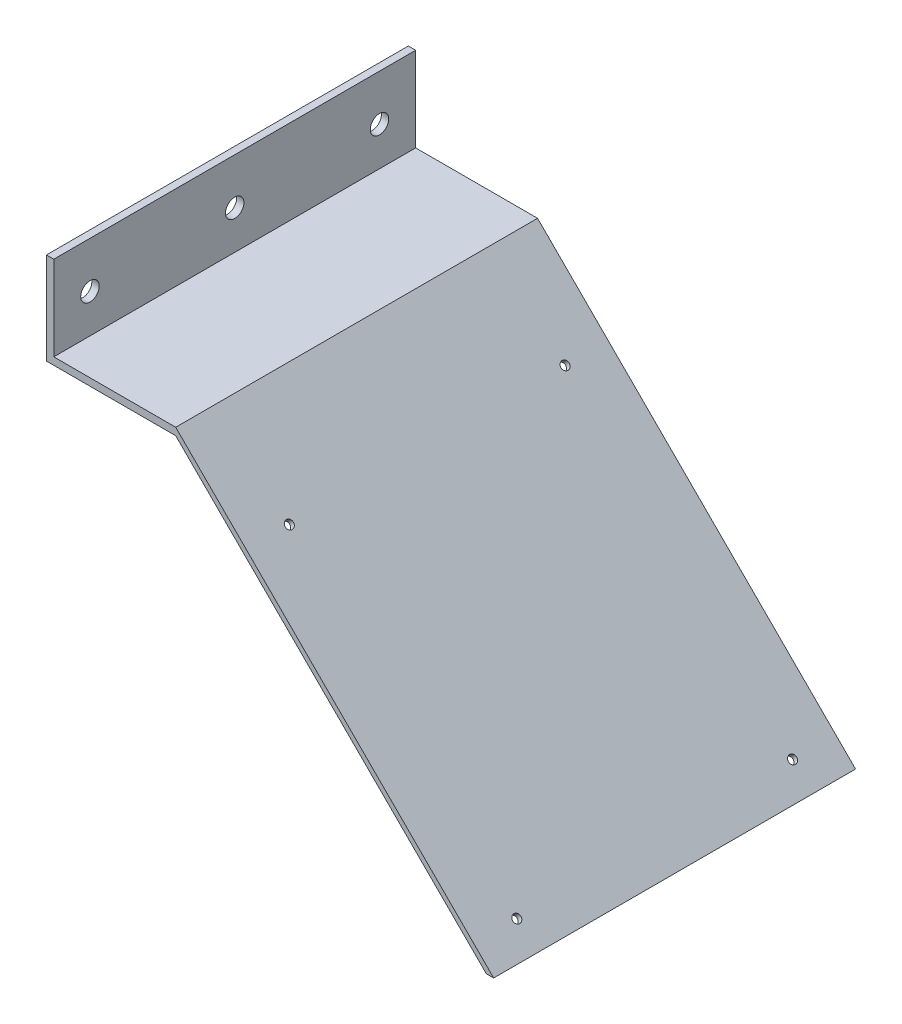
SolidWorks part; units mm, degrees
ref_plane "Front Plane" through (0, 0, 0) normal (0, 0, 1) x (1, 0, 0)
ref_plane "Top Plane" through (0, 0, 0) normal (0, 1, 0) x (1, 0, 0)
ref_plane "Right Plane" through (0, 0, 0) normal (1, 0, 0) x (0, 0, -1)
sketch "Sketch1" plane through (0, 0, 0) normal (0, 0, 1) x (1, 0, 0)
  line L0 (0, 0) -> (85.8336, -85.8336)
  line L9 (85.8336, -85.8336) -> (87.8656, -85.8336)
  line L10 (87.8656, -85.8336) -> (0, 2.032)
  line L12 (0, 2.032) -> (0, 0) construction
  line L13 (0, 0) -> (-35.7216, 0)
  line L14 (0, 0) -> (0, 2.032)
  line L15 (0, 2.032) -> (-35.7216, 2.032)
  line L16 (-35.7216, 0) -> (-35.7216, 2.032)
  line L17 (-35.7216, 0) -> (-33.6896, 0)
  line L18 (-35.7216, 0) -> (-35.7216, 25.4)
  line L19 (-35.7216, 25.4) -> (-33.6896, 25.4)
  line L20 (-33.6896, 0) -> (-33.6896, 25.4)
  line L21 (1.016, 1.016) -> (0, 0) construction
  dimension "D1" = 45
  dimension "D4" = 121.387
  dimension "D2" = 2.032
  dimension "D3" = 35.7216
  dimension "D5" = 25.4
  dimension "D7" = 1.4368
extrude "Boss-Extrude1" add sketch "Sketch1" along normal blind 100 contours L10 L12 L0 L9 | L20 L13 L14 L15 | L15 L20 L19 L18 | L13 L20 L15 L16 region at (43.4268, -42.4068, 0) region at (-16.8448, 1.016, 0) region at (-34.7056, 1.016, 0) region at (-34.7056, 13.716, 0)
sketch "Sketch2" plane through (1.016, 1.016, 0) normal (0.7071, 0.7071, 0) x (0, 0, -1)
  line L0 (-50, -28.087) -> (-50, -113.087) construction
  line L1 (-80, -28.087) -> (-20, -28.087) construction
  line L2 (-80, -28.087) -> (-80, -113.087) construction
  line L3 (-80, -113.087) -> (-20, -113.087) construction
  line L4 (-20, -28.087) -> (-20, -113.087) construction
  line L5 (-75, -35.187) -> (-25, -35.187) construction
  line L6 (-75, -35.187) -> (-75, -105.987) construction
  line L7 (-75, -105.987) -> (-25, -105.987) construction
  line L10 (-25, -35.187) -> (-25, -105.987) construction
  line L11 (-69.455, -33.889) -> (-30.545, -33.889) construction
  line L12 (-69.455, -33.889) -> (-69.455, -107.285) construction
  line L13 (-69.455, -107.285) -> (-30.545, -107.285) construction
  line L14 (-30.545, -33.889) -> (-30.545, -107.285) construction
  line L15 (-80, -70.587) -> (-20, -70.587) construction
  line L17 (-100, -122.8238) -> (0, -122.8238) construction
  line L19 (-100, -122.8238) -> (-100, 1.4368) construction
  line L21 (-88.1, -26.137) -> (-88.1, -115.037) construction
  line L22 (-88.1, -115.037) -> (-11.9, -115.037) construction
  line L23 (-11.9, -115.037) -> (-11.9, -26.137) construction
  line L24 (-11.9, -26.137) -> (-88.1, -26.137) construction
  circle A0 centre (-88.1, -26.137) radius 1.13
  circle A1 centre (-11.9, -26.137) radius 1.13
  circle A2 centre (-11.9, -115.037) radius 1.13
  circle A3 centre (-88.1, -115.037) radius 1.13
  point P6 (-25, -70.587)
  point P10 (-50, -28.087)
  point P13 (-50, -70.587)
  point P17 (-50, -35.187)
  point P23 (-50, -33.889)
  point P24 (-30.545, -70.587)
  point P37 (-50, -26.137)
  point P39 (-11.9, -70.587)
  dimension "D12" = 2.26
  dimension "D2" = 9.7368
  dimension "D3" = 50
  dimension "D11" = 76.2
  dimension "D13" = 88.9
ref_axis "Axis1" through (-9.134, -48.8965, 50) along (1, 0, 0)
extrude "Cut-Extrude1" cut sketch "Sketch2" against normal through all both and the other way through all
hole_wizard "#4-40 Tapped Hole1" positions "3DSketch1" profile "Sketch3" tap size "#4-40" standard "ANSI Inch" end condition through all
sketch3d "3DSketch1"
  point P0 (19.4977, -17.4657, 88.1)
  point P3 (19.4977, -17.4657, 11.9)
  point P6 (82.3594, -80.3274, 11.9)
  point P9 (82.3594, -80.3274, 88.1)
sketch "Sketch3" plane through (19.4977, -17.4657, 88.1) normal (0, 0, 1) x (-0.7071, 0.7071, 0)
  line L0 (0, 0) -> (0, 87.3893)
  line L1 (0, 87.3893) -> (1.1303, 87.3893)
  line L2 (1.1303, 87.3893) -> (1.1303, 0)
  line L5 (1.1303, 0) -> (0, 0)
  line L11 (0, -6.35) -> (0, 107.95) construction
  dimension "Thru Tap Drill Dia." = 2.2606
  dimension "Thru Tap Drill Depth" = 87.3893
cosmetic thread "Hole Thread1" parameters "D2"=2.8448
cosmetic thread "Hole Thread2" parameters "D2"=2.8448
cosmetic thread "Hole Thread3" parameters "D2"=2.8448
cosmetic thread "Hole Thread4" parameters "D2"=2.8448
hole_wizard "1/4-20 Tapped Hole1" positions "Sketch4" profile "Sketch5" tap size "1/4-20" standard "ANSI Inch" end condition through all
sketch "Sketch4" plane through (-35.7216, 0, 0) normal (-1, 0, 0) x (0, 0, 1)
  line L0 (10, 12.7) -> (50, 12.7) construction
  line L1 (50, 12.7) -> (90, 12.7) construction
  line L4 (0, 0) -> (0, 25.4) construction
  point P0 (10, 12.7)
  point P2 (50, 12.7)
  point P4 (90, 12.7)
  dimension "D1" = 80
  dimension "D2" = 10
  dimension "D3" = 12.7
sketch "Sketch5" plane through (-35.7216, 12.7, 10) normal (0, 1, 0) x (0, 0, 1)
  line L0 (0, 0) -> (0, 123.5871)
  line L1 (0, 123.5871) -> (2.5527, 123.5871)
  line L2 (2.5527, 123.5871) -> (2.5527, 0)
  line L5 (2.5527, 0) -> (0, 0)
  line L11 (0, -6.35) -> (0, 107.95) construction
  dimension "Thru Tap Drill Dia." = 5.1054
  dimension "Thru Tap Drill Depth" = 123.5871
cosmetic thread "Hole Thread5" parameters "D2"=6.35
cosmetic thread "Hole Thread6" parameters "D2"=6.35
cosmetic thread "Hole Thread7" parameters "D2"=6.35
equation "\"width\"=100"
equation "\"D1@Boss-Extrude1\"=\"width\""
equation "\"height\"=121.387"
equation "\"D4@Sketch1\"=\"height\""
equation "\"D3@Sketch2\"=100/2"
equation "\"D13@Sketch2\"=3.5*25.4"
equation "\"D11@Sketch2\"=3.0*25.4"
equation "\"D2@Sketch4\"=(100-\"D1@Sketch4\")/2"
